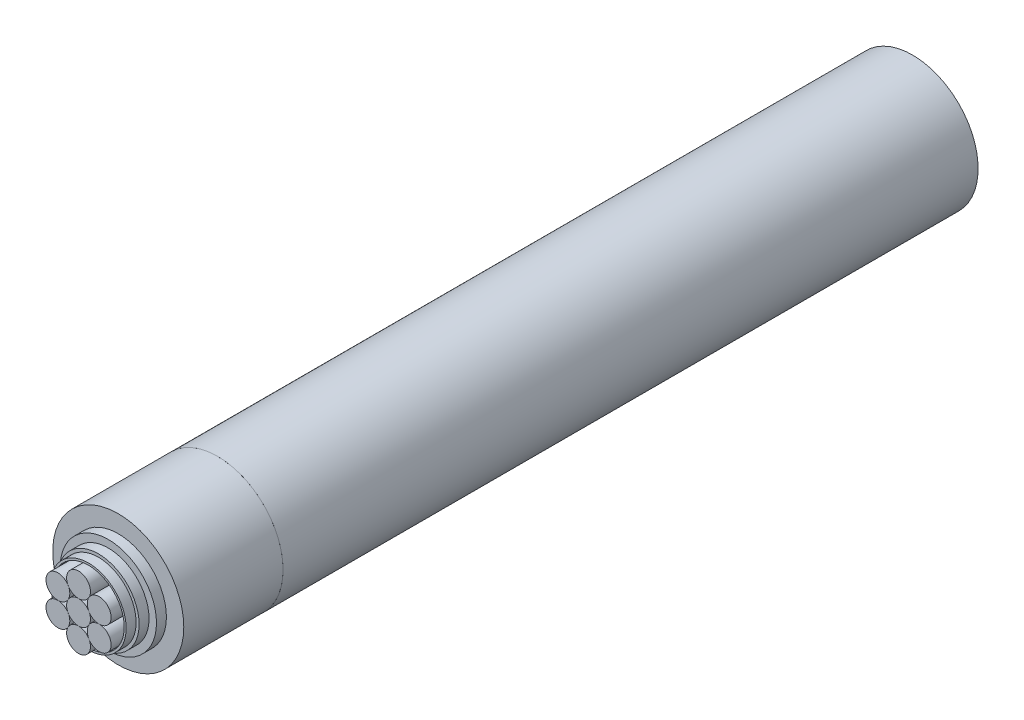
SolidWorks part; units mm, degrees
ref_plane "Ön Düzlem" through (0, 0, 0) normal (0, 0, 1) x (1, 0, 0)
ref_plane "Üst Düzlem" through (0, 0, 0) normal (0, 1, 0) x (1, 0, 0)
ref_plane "Sağ Düzlem" through (0, 0, 0) normal (1, 0, 0) x (0, 0, -1)
sketch "Çizim1" plane through (0, 0, 0) normal (0, 0, 1) x (1, 0, 0)
  circle A0 centre (0, 0) radius 6.6
  circle A1 centre (0, 0) radius 1.2
  circle A2 centre (0, 2.4) radius 1.2
  circle A3 centre (2.0785, 1.2) radius 1.2
  circle A4 centre (2.0785, -1.2) radius 1.2
  circle A5 centre (0, -2.4) radius 1.2
  circle A6 centre (-2.0785, -1.2) radius 1.2
  circle A7 centre (-2.0785, 1.2) radius 1.2
  circle A8 centre (0, 0) radius 3.6
  circle A9 centre (0, 0) radius 3.8
  circle A10 centre (0, 0) radius 4.85
  circle A11 centre (0, 0) radius 4.1
  point P18 (0, 0)
  dimension "D1" = 13.2
  dimension "D2" = 2.4
  dimension "D3" = 2.4
  dimension "D6" = 1.2
  dimension "D7" = 3.6
  dimension "D9" = 0.2
  dimension "D10" = 1.25
  dimension "D11" = 0.3
  dimension "D4" = 2.4
  dimension "D8" = 4.8
  dimension "D5" = 6
extrude "Yükseklik-Ekstrüzyon1" add sketch "Çizim1" along normal blind 10 contours A0 A10 region at (-6.4133, 0, 0)
extrude "Yükseklik-Ekstrüzyon2" add sketch "Çizim1<5>" along normal blind 11 contours A10 A11 region at (-4.7128, 0, 0)
sketch "Çizim1<5>" plane through (0, 0, 0) normal (0, 0, 1) x (1, 0, 0) same geometry as "Çizim1"
extrude "Yükseklik-Ekstrüzyon3" add sketch "Çizim1<6>" along normal blind 12 contours A11 A9 region at (-3.984, 0, 0)
sketch "Çizim1<6>" plane through (0, 0, 0) normal (0, 0, 1) x (1, 0, 0) same geometry as "Çizim1"
extrude "Yükseklik-Ekstrüzyon4" add sketch "Çizim1<7>" along normal blind 13 contours A9 A8 region at (-3.6925, 0, 0)
sketch "Çizim1<7>" plane through (0, 0, 0) normal (0, 0, 1) x (1, 0, 0) same geometry as "Çizim1"
extrude "Yükseklik-Ekstrüzyon5" add sketch "Çizim1<8>" along normal blind 14 separate body contours A7 | A6 | A5 | A4 | A3 | A2 | A1 region at (0, 0, 0) region at (2.0785, 1.2, 0) region at (2.0785, -1.2, 0) region at (0, 2.4, 0) region at (0, -2.4, 0) region at (-2.0785, 1.2, 0) region at (-2.0785, -1.2, 0)
sketch "Çizim1<8>" plane through (0, 0, 0) normal (0, 0, 1) x (1, 0, 0) same geometry as "Çizim1"
scale "Ölçek6" bodies to scale 108 107 106 105 111 109 110 104 scale about origin uniform scaling yes scale factor 0.5
sketch "Çizim3" plane through (0, 0, 0) normal (0, 0, -1) x (-1, 0, 0)
  circle A0 centre (0, 0) radius 3.3
extrude "Yükseklik-Ekstrüzyon8" add sketch "Çizim3" along normal blind 35 separate body
